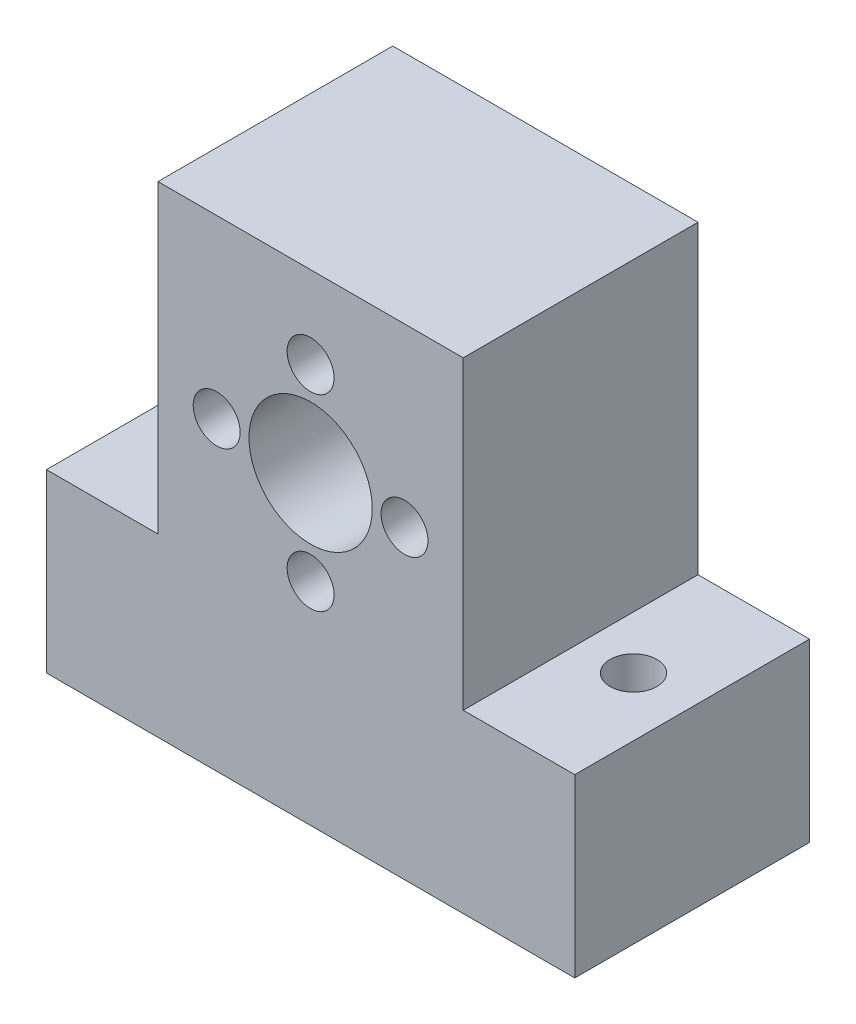
SolidWorks part; units mm, degrees
ref_plane "Front Plane" through (0, 0, 0) normal (0, 0, 1) x (1, 0, 0)
ref_plane "Top Plane" through (0, 0, 0) normal (0, 1, 0) x (1, 0, 0)
ref_plane "Right Plane" through (0, 0, 0) normal (1, 0, 0) x (0, 0, -1)
sketch "Sketch1" plane through (0, 0, 0) normal (0, 0, 1) x (1, 0, 0)
  line L0 (0, -438.3722) -> (0, 21480.2356) construction
  line L1 (-438.3722, 0) -> (21480.2356, 0) construction
  line L3 (-22.5, -26) -> (22.5, -26)
  line L4 (-22.5, -26) -> (-22.5, 15)
  line L5 (-22.5, 15) -> (22.5, 15)
  line L6 (22.5, -26) -> (22.5, 15)
  circle A0 centre (0, 0) radius 5.25
  circle A1 centre (0, 0) radius 8 construction
  circle A2 centre (0, 8) radius 2
  circle A3 centre (8, 0) radius 2
  circle A4 centre (0, -8) radius 2
  circle A5 centre (-8, 0) radius 2
  point P4 (0, 0)
  point P24 (0, 0)
  dimension "D2" = 10.5
  dimension "D4" = 16
  dimension "D5" = 4
  dimension "D7" = 8
  dimension "D8" = 8
  dimension "D1" = 15
  dimension "D3" = 45
  dimension "D9" = 26
  dimension "D10" = 22.5
  dimension "D6" = 4
extrude "Boss-Extrude1" add sketch "Sketch1" along normal blind 20
sketch "Sketch2" plane through (0, 15, 0) normal (0, 1, 0) x (1, 0, 0)
  line L0 (0, -1000) -> (0, 49000) construction
  line L1 (-1030, -10) -> (48970, -10) construction
  line L2 (-22.5, -20) -> (-22.5, 0) construction
  circle A0 centre (-17.5, -10) radius 2
  circle A1 centre (17.5, -10) radius 2
  point P8 (-22.5, -10)
  dimension "D2" = 4
  dimension "D1" = 5
extrude "Cut-Extrude1" cut sketch "Sketch2" against normal through all
sketch "Sketch3" plane through (0, 0, 0) normal (0, 0, -1) x (-1, 0, 0)
  line L0 (0, -1000) -> (0, 49000) construction
  line L1 (-1000, 0) -> (49000, 0) construction
  line L2 (-22.5, 15) -> (22.5, 15) construction
  line L3 (22.5, -26) -> (13, -26)
  line L4 (22.5, -26) -> (22.5, 15)
  line L5 (22.5, 15) -> (13, 15)
  line L6 (13, -26) -> (13, 15)
  line L7 (22.5, -11) -> (13, -11)
  line L8 (-22.5, -11) -> (-13, -11)
  line L9 (-13, -26) -> (-13, 15)
  line L10 (-22.5, 15) -> (-13, 15)
  line L11 (-22.5, -26) -> (-22.5, 15)
  line L12 (-22.5, -26) -> (-13, -26)
  line M7 (-22.5, 15) -> (-22.5, -26)
  line M10 (22.5, 15) -> (-22.5, 15)
  dimension "D1" = 13
  dimension "D2" = 15
extrude "Cut-Extrude2" cut sketch "Sketch3" against normal through all contours L7 L4 L6 M10 | L8 L9 M10 M7 region at (17.75, 2, 0) region at (-17.75, 2, 0)
